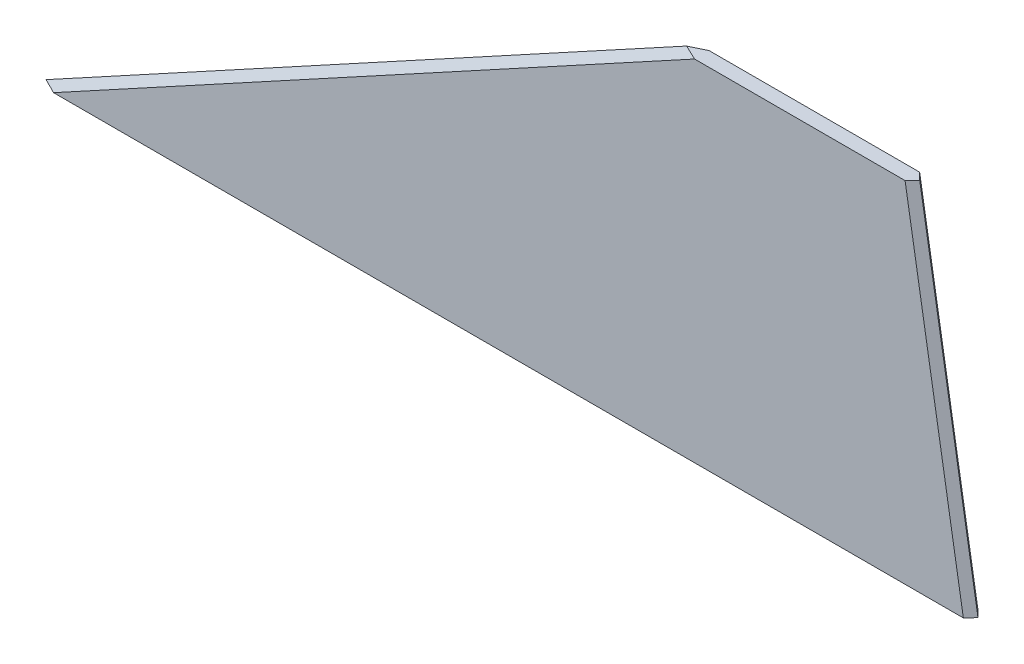
SolidWorks part; units mm, degrees
material "S-Glass Fiber"
ref_plane "Front Plane" through (0, 0, 0) normal (0, 0, 1) x (1, 0, 0)
ref_plane "Top Plane" through (0, 0, 0) normal (0, 1, 0) x (1, 0, 0)
ref_plane "Right Plane" through (0, 0, 0) normal (1, 0, 0) x (0, 0, -1)
sketch "Sketch1" plane through (0, 0, 0) normal (0, 0, 1) x (1, 0, 0)
  line L0 (0, 0) -> (406.4, 0)
  line L1 (279.4, 0) -> (279.4, 152.4) construction
  line L2 (0, 0) -> (279.4, 152.4)
  line L3 (279.4, 152.4) -> (381, 152.4)
  line L4 (406.4, 0) -> (381, 152.4)
  point P3 (279.4, 0)
  dimension "D1" = 406.4
  dimension "D2" = 279.4
  dimension "D3" = 152.4
  dimension "D4" = 101.6
extrude "Boss-Extrude1" add sketch "Sketch1" along normal blind 6.35 contours L2 L0 L1 | L0 L4 L3 L1 region at (186.2667, 50.8, 0) region at (336.7852, 73.3778, 0)
chamfer "Chamfer1" distance 3.175 distance2 3.175 4 edges at (393.7, 76.2, 6.35) (393.7, 76.2, 0) (139.7, 76.2, 0) (139.7, 76.2, 6.35)
sketch "Sketch2" plane through (0, 0, 0) normal (1, 0, 0) x (0, 0, -1)
  circle A0 centre (-3.175, -50.7007) radius 50.8
  dimension "D3" = 101.6
  dimension "D1" = 50.8
  dimension "D2" = 50.8
extrude "Cut-Extrude1" cut sketch "Sketch2" along normal blind 421.64 and the other way blind 27.432
